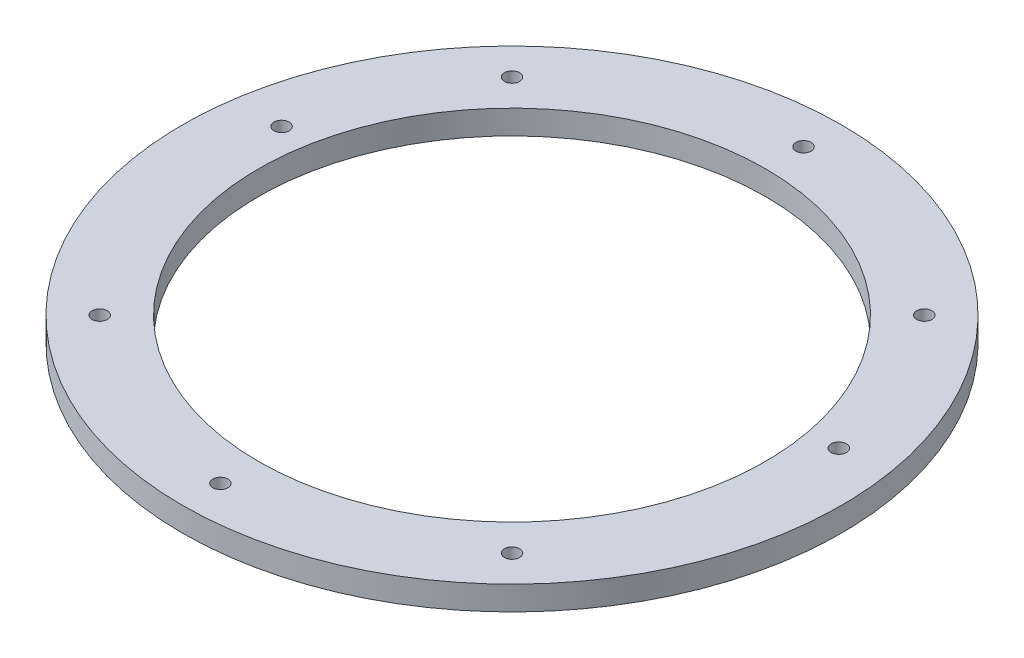
SolidWorks part; units mm, degrees
note: '?' marks a value the reader was unsure of.
ref_plane "Front Plane" through (0, 0, 0) normal (0, 0, 1) x (1, 0, 0)
ref_plane "Top Plane" through (0, 0, 0) normal (0, 1, 0) x (1, 0, 0)
ref_plane "Right Plane" through (0, 0, 0) normal (1, 0, 0) x (0, 0, -1)
sketch "Sketch1" plane through (0, 0, 0) normal (0, 1, 0) x (1, 0, 0)
  circle A0 centre (0, 0) radius 50
  circle A1 centre (0, 0) radius 65
extrude "Boss-Extrude1" add sketch "Sketch1" along normal blind 4.75
sketch "Sketch2" plane through (0, 4.75, 0) normal (0, 1, 0) x (1, 0, 0)
  line L0 (0, -50) -> (0, 50) construction
  line L1 (-50, 0) -> (50, 0) construction
  line L2 (-35.3553, -35.3553) -> (35.3553, 35.3553) construction
  line L3 (-35.3553, 35.3553) -> (35.3553, -35.3553) construction
  line L4 (35.3553, 35.3553) -> (45.9619, 45.9619) construction
  line L5 (50, 0) -> (65, 0) construction
  line L6 (35.3553, -35.3553) -> (45.9619, -45.9619) construction
  line L7 (0, -50) -> (0, -65) construction
  circle A0 centre (0, 0) radius 50 construction
  circle A1 centre (0, 0) radius 65 construction
  circle A2 centre (40.6586, 40.6586) radius 1.5
  circle A4 centre (40.6586, -40.6586) radius 1.5
  circle A5 centre (0, -57.5) radius 1.5
  circle A6 centre (-40.6586, 40.6586) radius 1.5
  circle A7 centre (0, 57.5) radius 1.5
  circle A9 centre (-40.6586, -40.6586) radius 1.5
  point P7 (0, 0)
  point P11 (0, 0)
  point P14 (0, 0)
  point P17 (0, 0)
extrude "Cut-Extrude1" cut sketch "Sketch2" against normal blind 5
sketch "Sketch3" plane through (0, 4.75, 0) normal (0, 1, 0) x (1, 0, 0)
  line L0 (0, 0) -> (0, 24.0218) construction
  circle A0 centre (54.9519, 9.5) radius 1.5
  circle A1 centre (-54.9519, 9.5) radius 1.5
extrude "Cut-Extrude2" cut sketch "Sketch3" against normal through all
convert to sheet metal "Convert-Solid1" [suppressed] bend radius? 10 thickness? 4.75
sketch "Bend-Lines1" [suppressed] plane through (0, 0, 0) normal (0, 1, 0) x (1, 0, 0)
sketch "Bounding-Box1" [suppressed] plane through (0, 0, 0) normal (0, 1, 0) x (1, 0, 0)
sheet metal parameters "Sheet-Metal7" thickness 4.75 parameters "D1"=10
flat pattern "Flat-Pattern7" [suppressed]
sketch "Bend-Lines2" plane through (0, 0, 0) normal (0, 1, 0) x (1, 0, 0)
sketch3d "Bounding-Box2" [suppressed]
  line L0 (-65.0447, 64.9552, 0) -> (-64.9552, -65.0447, 0) construction
  line L1 (64.9552, 65.0447, 0) -> (65.0447, -64.9552, 0) construction
  line L2 (-65.0447, 64.9552, 0) -> (64.9552, 65.0447, 0) construction
  line L3 (-64.9552, -65.0447, 0) -> (65.0447, -64.9552, 0) construction
